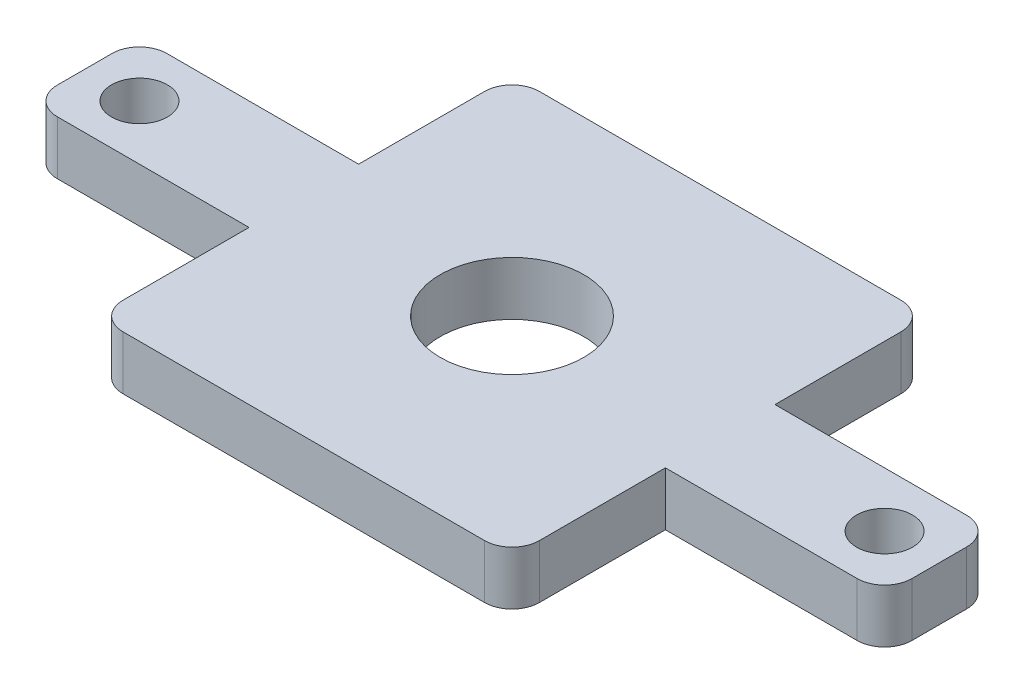
SolidWorks part; units mm, degrees
ref_plane "Front Plane" through (0, 0, 0) normal (0, 0, 1) x (1, 0, 0)
ref_plane "Top Plane" through (0, 0, 0) normal (0, 1, 0) x (1, 0, 0)
ref_plane "Right Plane" through (0, 0, 0) normal (1, 0, 0) x (0, 0, -1)
sketch "Sketch1" plane through (0, 0, 0) normal (0, 1, 0) x (1, 0, 0)
  line L0 (0, 0) -> (34, 0) construction
  line L1 (-19, -19) -> (19, -19)
  line L2 (-19, -19) -> (-19, 19)
  line L3 (-19, 19) -> (19, 19)
  line L4 (19, -19) -> (19, 19)
  line L5 (-19, -19) -> (19, 19) construction
  line L6 (-19, 19) -> (19, -19) construction
  line L7 (29, 5) -> (19, 5)
  line L8 (29, -5) -> (39, -5)
  line L9 (29, -5) -> (29, 5) construction
  line L10 (29, 5) -> (39, 5)
  line L11 (39, -5) -> (39, 5)
  line L12 (29, -5) -> (39, 5) construction
  line L13 (29, 5) -> (39, -5) construction
  line L14 (29, -5) -> (19, -5)
  line L15 (0, 19) -> (0, -19) construction
  line L16 (-29, 5) -> (-19, 5)
  line L17 (-29, -5) -> (-19, -5)
  line L18 (-29, -5) -> (-39, -5)
  line L19 (-39, -5) -> (-39, 5)
  line L20 (-29, 5) -> (-39, 5)
  circle A0 centre (0, 0) radius 18.75 construction
  circle A1 centre (34, 0) radius 2.55
  circle A2 centre (-34, 0) radius 2.55
  circle A3 centre (0, 0) radius 6.55
  dimension "D1" = 37.5
  dimension "D4" = 5.1
  dimension "D6" = 13.1
  dimension "D2" = 38
  dimension "D3" = 34
  dimension "D5" = 10
extrude "Boss-Extrude1" add sketch "Sketch1" along normal blind 4.9 contours L1 L4 L3 L2 A3 | L16 L20 L19 L18 L17 L2 A2 | L14 L8 L11 L10 L7 L4 A1 region at (-18.4626, 0, 12) region at (-28.4312, 0, 0) region at (28.4312, 0, 0)
fillet "Fillet1" radius 2.5 8 edges at (39, 2.45, -5) (39, 2.45, 5) (-39, 2.45, -5) (-39, 2.45, 5) (19, 2.45, 19) (-19, 2.45, 19) (-19, 2.45, -19) (19, 2.45, -19)
